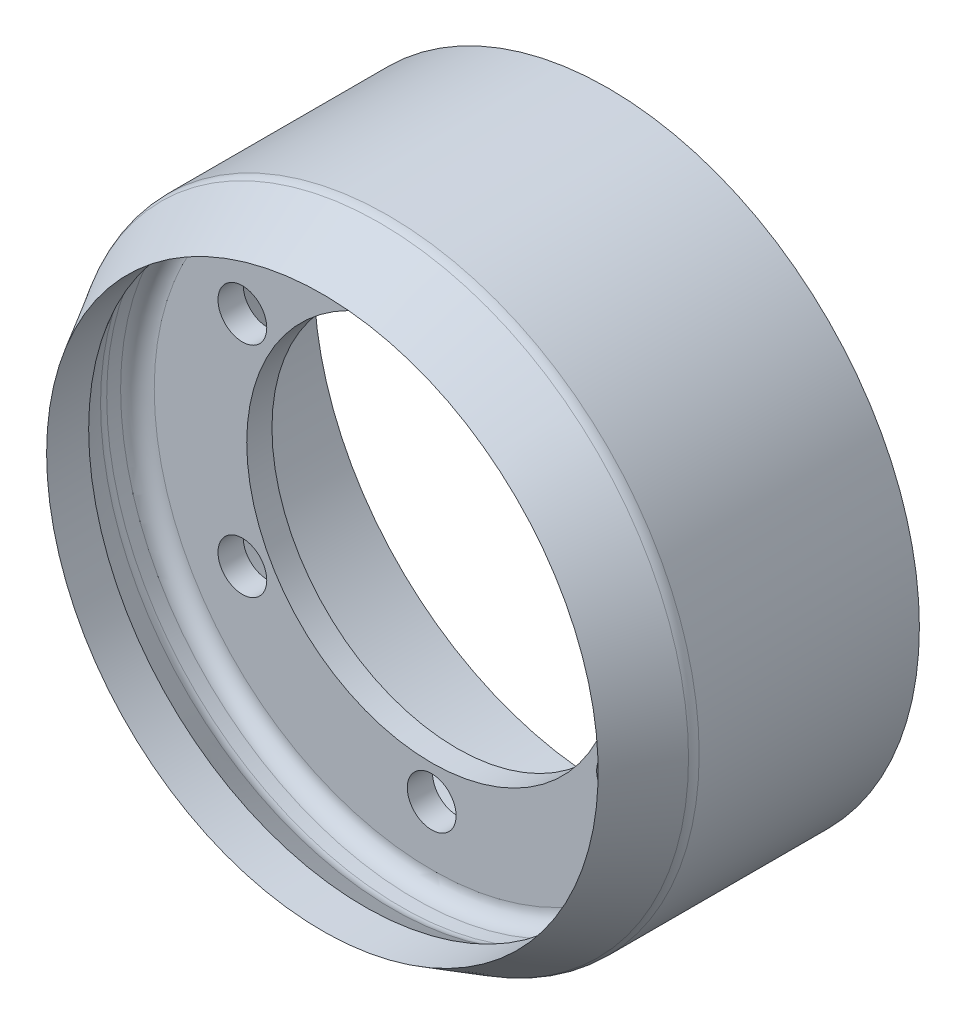
SolidWorks part; units mm, degrees
material "AISI Type 316L stainless steel"
ref_plane "Front Plane" through (0, 0, 0) normal (0, 0, 1) x (1, 0, 0)
ref_plane "Top Plane" through (0, 0, 0) normal (0, 1, 0) x (1, 0, 0)
ref_plane "Right Plane" through (0, 0, 0) normal (1, 0, 0) x (0, 0, -1)
sketch "Sketch1" plane through (0, 0, 0) normal (1, 0, 0) x (0, 0, -1)
  line L0 (0, 0) -> (-39.4421, 0) construction
  line L1 (-8, 16.4) -> (-4.5947, 18.366)
  line L2 (-4.0947, 18.5) -> (9, 18.5)
  line L3 (9, 18.5) -> (9, 17.5)
  line L4 (9, 17.5) -> (0, 17.5)
  line L5 (0, 17.5) -> (0, 11)
  line L6 (0, 11) -> (-1.5, 11)
  line L7 (-1.5, 11) -> (-1.5, 16.5)
  line L8 (-2.5, 17.5) -> (-3.3268, 17.5)
  line L9 (-3.8268, 17.366) -> (-5.5, 16.4)
  line L10 (-5.5, 16.4) -> (-8, 16.4)
  arc A0 (-4.5947, 18.366) -> (-4.0947, 18.5) centre (-4.0947, 17.5) cw
  arc A1 (-1.5, 16.5) -> (-2.5, 17.5) centre (-2.5, 16.5) ccw
  arc A2 (-3.3268, 17.5) -> (-3.8268, 17.366) centre (-3.3268, 16.5) ccw
  dimension "D10" = 1
  dimension "D1" = 22
  dimension "D2" = 35
  dimension "D3" = 37
  dimension "D4" = 32.8
  dimension "D5" = 17
  dimension "D6" = 1.5
  dimension "D7" = 4
  dimension "D8" = 9
  dimension "D9" = 30
revolve "Revolve1" add sketch "Sketch1" angle 360 about L0
hole_wizard "M2.5 Clearance Hole1" positions "Sketch3" profile "Sketch2" hole size "M2.5" standard "ANSI Metric"
sketch "Sketch3" plane through (0, 0, 1.5) normal (0, 0, 1) x (1, 0, 0)
  point P0 (0, 13)
  dimension "D1" = 13
sketch "Sketch2" plane through (0, 13, 1.5) normal (1, 0, 0) x (0, -1, 0)
  line L0 (0, 0) -> (0, 23.8712)
  line L1 (0, 23.8712) -> (1.45, 23)
  line L2 (1.45, 23) -> (1.45, 0)
  line L5 (1.45, 0) -> (0, 0)
  line L10 (0, 23.8712) -> (-1.45, 23) construction
  line L11 (0, -6.35) -> (0, 107.95) construction
  dimension "Hole Dia." = 2.9
  dimension "Hole Depth" = 23
  dimension "Drill Angle" = 118
ref_axis "Axis1" through (0, 0, 4.0947) along (0, 0, -1)
pattern_circular "CirPattern1" count 6 over 360 about axis through (0, 0, 4.0947) along (0, 0, -1) of "M2.5 Clearance Hole1"
